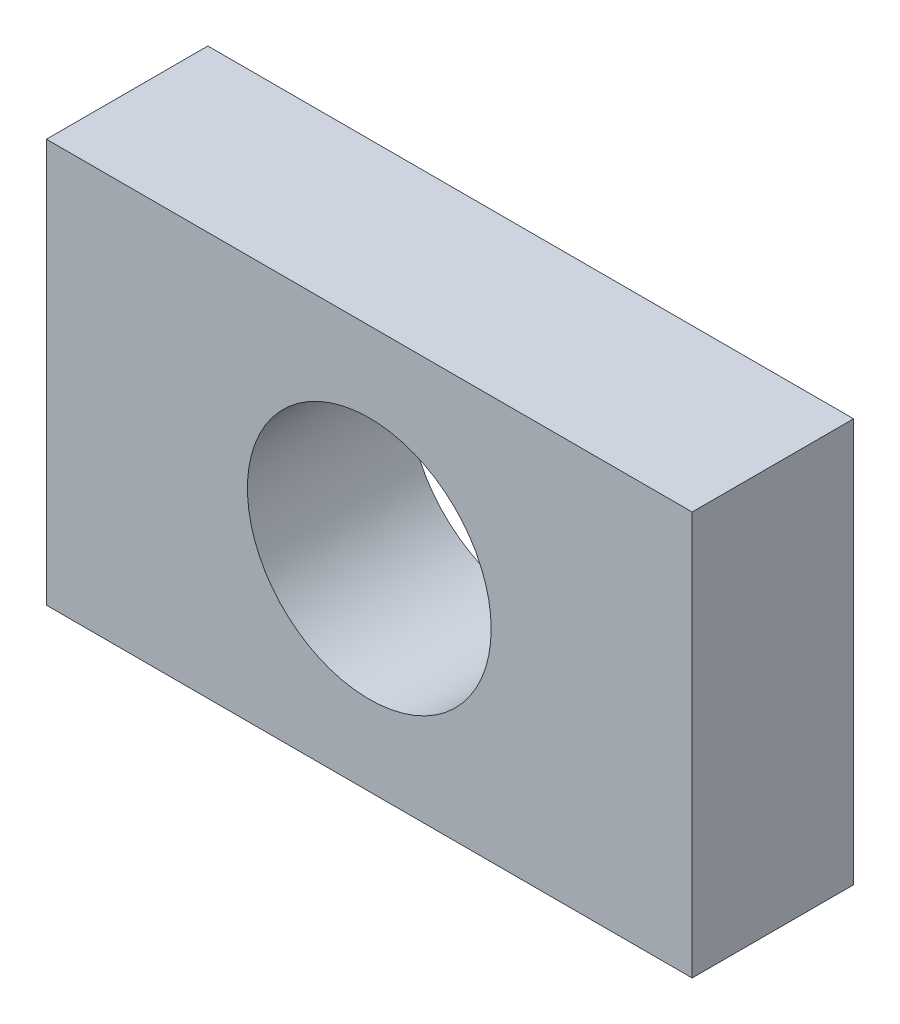
SolidWorks part; units mm, degrees
material "AISI 304"
ref_plane "Front Plane" through (0, 0, 0) normal (0, 0, 1) x (1, 0, 0)
ref_plane "Top Plane" through (0, 0, 0) normal (0, 1, 0) x (1, 0, 0)
ref_plane "Right Plane" through (0, 0, 0) normal (1, 0, 0) x (0, 0, -1)
sketch "Bearing_Block_Profile" plane through (0, 0, 0) normal (0, 0, 1) x (1, 0, 0)
  line L1 (-40, -25) -> (40, -25)
  line L2 (-40, -25) -> (-40, 25)
  line L3 (-40, 25) -> (40, 25)
  line L4 (40, -25) -> (40, 25)
  line L5 (-40, -25) -> (40, 25) construction
  line L6 (-40, 25) -> (40, -25) construction
  circle A0 centre (0, 0) radius 15.1
  dimension "Bore_Diameter" = 30.2
  dimension "Half_Width" = 40
  dimension "Half_Height" = 25
extrude "Bearing_Block_Extrude" add sketch "Bearing_Block_Profile" along normal mid plane 20
ref_axis "Bore_Axis" through (0, 0, -11) along (0, 0, 1)
